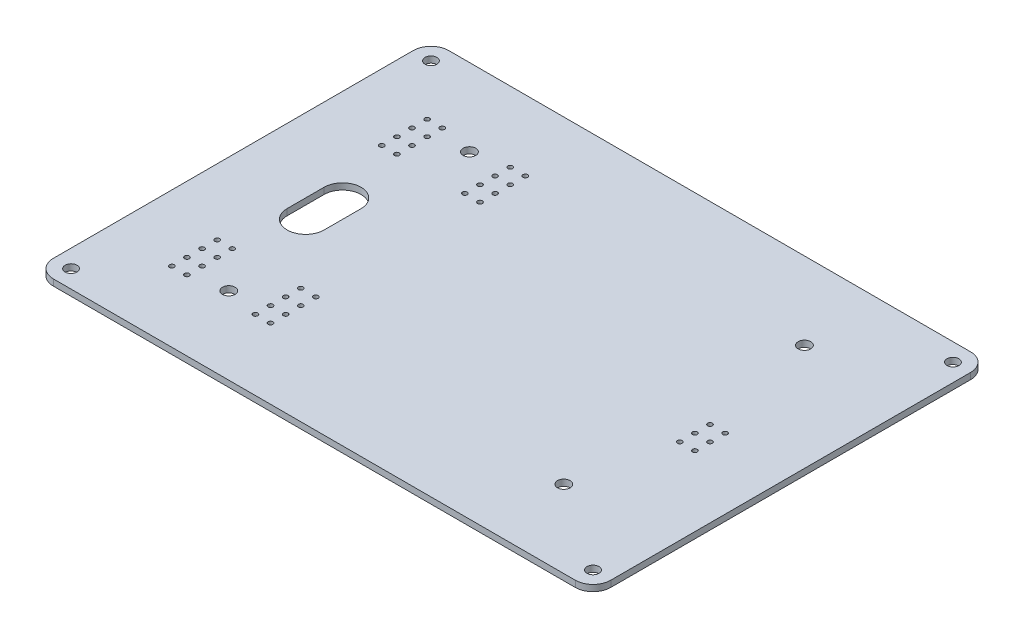
SolidWorks part; units mm, degrees
material "A-Glass Fiber"
ref_plane "Front Plane" through (0, 0, 0) normal (0, 0, 1) x (1, 0, 0)
ref_plane "Top Plane" through (0, 0, 0) normal (0, 1, 0) x (1, 0, 0)
ref_plane "Right Plane" through (0, 0, 0) normal (1, 0, 0) x (0, 0, -1)
sketch "Sketch1" plane through (0, 0, 0) normal (0, 1, 0) x (1, 0, 0)
  line L0 (0, 0) -> (70.7165, 0) construction
  line L1 (-65.4106, -49.8688) -> (66.2376, -49.8688)
  line L2 (-69.8896, -45.3898) -> (-69.8896, 45.3898)
  line L3 (-65.4106, 49.8688) -> (66.2376, 49.8688)
  line L4 (70.7165, -45.3898) -> (70.7165, 45.3898)
  line L5 (-69.8896, -49.8688) -> (70.7165, 49.8688) construction
  line L6 (-69.8896, 49.8688) -> (70.7165, -49.8688) construction
  line L10 (-71.1596, 54.5719) -> (-71.1596, 45.5295) construction
  arc A0 (-69.8896, 45.3898) -> (-65.4106, 49.8688) centre (-65.4106, 45.3898) cw
  arc A1 (66.2376, 49.8688) -> (70.7165, 45.3898) centre (66.2376, 45.3898) cw
  arc A2 (70.7165, -45.3898) -> (66.2376, -49.8688) centre (66.2376, -45.3898) cw
  arc A3 (-65.4106, -49.8688) -> (-69.8896, -45.3898) centre (-65.4106, -45.3898) cw
  point P0 (0.4135, 0)
  point P8 (66.2581, 45.3898)
  point P9 (-67.329, 45.3898)
  point P12 (0, 0)
  point P13 (-68.7024, 48.7021)
  point P15 (-70.1912, 50.1909)
  dimension "D1" = 1.27
extrude "Boss-Extrude1" add sketch "Sketch1" against normal blind 1.5875
sketch "Sketch2" plane through (0, 0, 0) normal (0, 1, 0) x (1, 0, 0)
  circle A35 centre (-40.6725, -30.35) radius 1.5875
  circle A36 centre (-40.6725, -30.35) radius 1.5875
  circle A37 centre (-40.6725, 30.35) radius 1.5875
  circle A38 centre (-40.6725, 30.35) radius 1.5875
  circle A39 centre (43.8275, 30.35) radius 1.5875
  circle A40 centre (43.8275, 30.35) radius 1.5875
  circle A41 centre (43.8275, -30.35) radius 1.5875
  circle A42 centre (43.8275, -30.35) radius 1.5875
  dimension "D27" = 0
  dimension "D28" = 0
  dimension "D29" = 0
  dimension "D30" = 0
extrude "Cut-Extrude1" cut sketch "Sketch2" against normal through all
sketch "Sketch3" plane through (0, 0, 0) normal (0, 1, 0) x (1, 0, 0)
  line L5 (-46.6035, 4.285) -> (-46.6035, -5.035) construction
  line L6 (-41.9335, 4.285) -> (-41.9335, -5.035)
  line L7 (-51.2735, 4.285) -> (-51.2735, -5.035)
  line L17 (-43.2035, 3.375) -> (-41.9335, 3.375) construction
  line L18 (-44.8535, 7.2) -> (-44.1998, 8.2889) construction
  line L19 (-46.6035, 7.2) -> (-46.6035, 8.955) construction
  line L20 (-44.8535, 7.2) -> (-48.3535, 7.2) construction
  line L21 (-46.6035, -7.95) -> (-46.6035, -9.705) construction
  line L22 (-48.3535, -7.95) -> (-44.8535, -7.95) construction
  arc A13 (-41.9335, 4.285) -> (-51.2735, 4.285) centre (-46.6035, 4.285) ccw
  arc A14 (-51.2735, -5.035) -> (-41.9335, -5.035) centre (-46.6035, -5.035) ccw
  arc A17 (-44.8535, 0.46) -> (-44.8535, 6.29) centre (-46.6035, 3.375) ccw construction
  point P2 (-46.6035, -0.375)
  dimension "D1" = 1.27
extrude "Cut-Extrude2" cut sketch "Sketch3" against normal through all
sketch "Sketch4" plane through (0, -1.5875, 0) normal (0, -1, 0) x (1, 0, 0)
  line L4 (-34.35, -10.348) -> (-39.27, -10.348)
  line L5 (-34.35, -25.08) -> (-34.35, -10.348)
  line L6 (-39.27, -25.08) -> (-34.35, -25.08)
  line L7 (-39.27, -10.348) -> (-39.27, -25.08)
  line L8 (-34.35, -10.348) -> (-39.27, -10.348)
  line L9 (-34.35, -25.08) -> (-34.35, -10.348)
  line L10 (-39.27, -25.08) -> (-34.35, -25.08)
  line L11 (-39.27, -10.348) -> (-39.27, -25.08)
  line L12 (-34.35, 25.63) -> (-39.27, 25.63)
  line L13 (-34.35, 10.898) -> (-34.35, 25.63)
  line L14 (-39.27, 10.898) -> (-34.35, 10.898)
  line L15 (-39.27, 25.63) -> (-39.27, 10.898)
  line L16 (-34.35, 25.63) -> (-39.27, 25.63)
  line L17 (-34.35, 10.898) -> (-34.35, 25.63)
  line L18 (-39.27, 10.898) -> (-34.35, 10.898)
  line L19 (-39.27, 25.63) -> (-39.27, 10.898)
  line L20 (-44.42, 10.898) -> (-39.5, 10.898)
  line L21 (-39.5, 10.898) -> (-39.5, 25.63)
  line L22 (-39.5, 25.63) -> (-44.42, 25.63)
  line L23 (-44.42, 25.63) -> (-44.42, 10.898)
  line L24 (-44.42, 10.898) -> (-39.5, 10.898)
  line L25 (-39.5, 10.898) -> (-39.5, 25.63)
  line L26 (-39.5, 25.63) -> (-44.42, 25.63)
  line L27 (-44.42, 25.63) -> (-44.42, 10.898)
  line L28 (-39.5, -10.348) -> (-44.42, -10.348)
  line L29 (-39.5, -25.08) -> (-39.5, -10.348)
  line L30 (-44.42, -25.08) -> (-39.5, -25.08)
  line L31 (-44.42, -10.348) -> (-44.42, -25.08)
  line L32 (-39.5, -10.348) -> (-44.42, -10.348)
  line L33 (-39.5, -25.08) -> (-39.5, -10.348)
  line L34 (-44.42, -25.08) -> (-39.5, -25.08)
  line L35 (-44.42, -10.348) -> (-44.42, -25.08)
  line L36 (35.46, 13.148) -> (40.38, 13.148)
  line L37 (35.46, 27.88) -> (35.46, 13.148)
  line L38 (40.38, 27.88) -> (35.46, 27.88)
  line L39 (40.38, 13.148) -> (40.38, 27.88)
  line L40 (35.46, 13.148) -> (40.38, 13.148)
  line L41 (35.46, 27.88) -> (35.46, 13.148)
  line L42 (40.38, 27.88) -> (35.46, 27.88)
  line L43 (40.38, 13.148) -> (40.38, 27.88)
  dimension "D1" = 0
  dimension "D2" = 0
  dimension "D3" = 0
  dimension "D4" = 0
  dimension "D5" = 0
sketch "Sketch6" plane through (0, -1.5875, 0) normal (0, -1, 0) x (1, 0, 0)
  line L0 (-20.19, 27.65) -> (-20.19, 33.65) construction
  line L1 (-20.19, 33.65) -> (-14.19, 33.65) construction
  line L2 (-14.19, 33.65) -> (-14.19, 27.65) construction
  line L3 (-14.19, 27.65) -> (-20.19, 27.65) construction
  line L4 (33.69, -6.45) -> (33.69, -22.45)
  line L5 (54.59, -6.45) -> (33.69, -6.45)
  line L6 (54.59, -22.45) -> (54.59, -6.45)
  line L7 (33.69, -22.45) -> (54.59, -22.45)
  line L8 (33.69, -6.45) -> (33.69, -22.45)
  line L9 (54.59, -6.45) -> (33.69, -6.45)
  line L10 (54.59, -22.45) -> (54.59, -6.45)
  line L11 (33.69, -22.45) -> (54.59, -22.45)
  line L20 (-8.69, 27.65) -> (-8.69, 33.65) construction
  line L21 (-8.69, 33.65) -> (-2.69, 33.65) construction
  line L22 (-2.69, 33.65) -> (-2.69, 27.65) construction
  line L23 (-2.69, 27.65) -> (-8.69, 27.65) construction
  line L24 (-20.19, 27.65) -> (-20.19, 33.65)
  line L25 (-20.19, 33.65) -> (-14.19, 33.65)
  line L26 (-14.19, 33.65) -> (-14.19, 27.65)
  line L27 (-14.19, 27.65) -> (-20.19, 27.65)
  line L28 (-8.69, 27.65) -> (-8.69, 33.65)
  line L29 (-8.69, 33.65) -> (-2.69, 33.65)
  line L30 (-2.69, 33.65) -> (-2.69, 27.65)
  line L31 (-2.69, 27.65) -> (-8.69, 27.65)
  line L80 (55.31, -35.15) -> (55.31, 35.15)
  line L82 (55.31, 35.15) -> (-55.31, 35.15)
  line L84 (-55.31, 35.15) -> (-55.31, -35.15)
  line L86 (-55.31, -35.15) -> (55.31, -35.15)
  line L92 (55.31, -35.15) -> (55.31, 35.15)
  line L94 (55.31, 35.15) -> (-55.31, 35.15)
  line L96 (-55.31, 35.15) -> (-55.31, -35.15)
  line L98 (-55.31, -35.15) -> (55.31, -35.15)
  circle A0 centre (-17.19, 30.65) radius 1.75 construction
  circle A1 centre (-5.69, 30.65) radius 1.75 construction
  circle A2 centre (-17.19, 30.65) radius 1.75
  circle A3 centre (-5.69, 30.65) radius 1.75
  dimension "D1" = 0
  dimension "D2" = 0
sketch "Sketch7" plane through (0, -1.5875, 0) normal (0, -1, 0) x (1, 0, 0)
  circle A1 centre (49.2175, 6.483) radius 0.6
  circle A2 centre (49.2175, 6.483) radius 0.6
  circle A3 centre (-49.3085, -32.125) radius 0.6
  circle A4 centre (-49.3085, -32.125) radius 0.6
  circle A5 centre (-28.3535, -32.125) radius 0.6
  circle A6 centre (-28.3535, -32.125) radius 0.6
  circle A7 centre (-28.3535, 20.707) radius 0.6
  circle A8 centre (-28.3535, 20.707) radius 0.6
  circle A9 centre (-49.4355, 20.707) radius 0.6
  circle A10 centre (-49.4355, 20.707) radius 0.6
  circle A11 centre (-32.1635, 20.707) radius 0.6
  circle A12 centre (-32.1635, 20.707) radius 0.6
  circle A13 centre (-53.2455, 20.707) radius 0.6
  circle A14 centre (-53.2455, 20.707) radius 0.6
  circle A15 centre (-32.1635, 28.327) radius 0.6
  circle A16 centre (-32.1635, 28.327) radius 0.6
  circle A17 centre (-53.2455, 28.327) radius 0.6
  circle A18 centre (-53.2455, 28.327) radius 0.6
  circle A19 centre (-32.1635, 24.517) radius 0.6
  circle A20 centre (-32.1635, 24.517) radius 0.6
  circle A21 centre (-53.2455, 24.517) radius 0.6
  circle A22 centre (-53.2455, 24.517) radius 0.6
  circle A23 centre (-32.1635, -28.315) radius 0.6
  circle A24 centre (-32.1635, -28.315) radius 0.6
  circle A25 centre (-53.1185, -28.315) radius 0.6
  circle A26 centre (-53.1185, -28.315) radius 0.6
  circle A27 centre (-32.1635, -32.125) radius 0.6
  circle A28 centre (-32.1635, -32.125) radius 0.6
  circle A29 centre (-53.1185, -32.125) radius 0.6
  circle A30 centre (-53.1185, -32.125) radius 0.6
  circle A31 centre (-28.3535, 24.517) radius 0.6
  circle A32 centre (-28.3535, 24.517) radius 0.6
  circle A33 centre (-49.4355, 24.517) radius 0.6
  circle A34 centre (-49.4355, 24.517) radius 0.6
  circle A35 centre (-32.1635, 32.137) radius 0.6
  circle A36 centre (-32.1635, 32.137) radius 0.6
  circle A37 centre (-53.2455, 32.137) radius 0.6
  circle A38 centre (-53.2455, 32.137) radius 0.6
  circle A39 centre (-32.1635, -20.695) radius 0.6
  circle A40 centre (-32.1635, -20.695) radius 0.6
  circle A41 centre (-53.1185, -20.695) radius 0.6
  circle A42 centre (-53.1185, -20.695) radius 0.6
  circle A43 centre (-32.1635, -24.505) radius 0.6
  circle A44 centre (-32.1635, -24.505) radius 0.6
  circle A45 centre (-53.1185, -24.505) radius 0.6
  circle A46 centre (-53.1185, -24.505) radius 0.6
  circle A47 centre (-28.3535, 32.137) radius 0.6
  circle A48 centre (-28.3535, 32.137) radius 0.6
  circle A49 centre (-49.4355, 32.137) radius 0.6
  circle A50 centre (-49.4355, 32.137) radius 0.6
  circle A51 centre (-28.3535, 28.327) radius 0.6
  circle A52 centre (-28.3535, 28.327) radius 0.6
  circle A53 centre (-49.4355, 28.327) radius 0.6
  circle A54 centre (-49.4355, 28.327) radius 0.6
  circle A55 centre (-28.3535, -24.505) radius 0.6
  circle A56 centre (-28.3535, -24.505) radius 0.6
  circle A57 centre (-49.3085, -24.505) radius 0.6
  circle A58 centre (-49.3085, -24.505) radius 0.6
  circle A59 centre (-28.3535, -28.315) radius 0.6
  circle A60 centre (-28.3535, -28.315) radius 0.6
  circle A61 centre (-49.3085, -28.315) radius 0.6
  circle A62 centre (-49.3085, -28.315) radius 0.6
  circle A63 centre (49.2175, 2.673) radius 0.6
  circle A64 centre (49.2175, 2.673) radius 0.6
  circle A65 centre (53.0275, -1.137) radius 0.6
  circle A66 centre (53.0275, -1.137) radius 0.6
  circle A67 centre (53.0275, 2.673) radius 0.6
  circle A68 centre (53.0275, 2.673) radius 0.6
  circle A69 centre (53.0275, 6.483) radius 0.6
  circle A70 centre (53.0275, 6.483) radius 0.6
  circle A71 centre (-28.3535, -20.695) radius 0.6
  circle A72 centre (-28.3535, -20.695) radius 0.6
  circle A73 centre (-49.3085, -20.695) radius 0.6
  circle A74 centre (-49.3085, -20.695) radius 0.6
  circle A75 centre (49.2175, -1.137) radius 0.6
  circle A76 centre (49.2175, -1.137) radius 0.6
  dimension "D1" = 0
  dimension "D2" = 0
  dimension "D3" = 0
  dimension "D4" = 0
  dimension "D5" = 0
  dimension "D6" = 0
  dimension "D7" = 0
  dimension "D8" = 0
  dimension "D9" = 0
  dimension "D10" = 0
  dimension "D11" = 0
  dimension "D12" = 0
  dimension "D13" = 0
  dimension "D14" = 0
  dimension "D15" = 0
  dimension "D16" = 0
  dimension "D17" = 0
  dimension "D18" = 0
  dimension "D19" = 0
  dimension "D20" = 0
  dimension "D21" = 0
  dimension "D22" = 0
  dimension "D23" = 0
  dimension "D24" = 0
  dimension "D25" = 0
  dimension "D26" = 0
  dimension "D27" = 0
  dimension "D28" = 0
  dimension "D29" = 0
  dimension "D30" = 0
  dimension "D31" = 0
  dimension "D32" = 0
  dimension "D33" = 0
  dimension "D34" = 0
  dimension "D35" = 0
  dimension "D36" = 0
  dimension "D37" = 0
  dimension "D38" = 0
extrude "Cut-Extrude3" cut sketch "Sketch7" against normal through all
sketch "Sketch8" plane through (0, -1.5875, 0) normal (0, -1, 0) x (1, 0, 0)
  line L4 (-48.1085, -18.395) -> (-54.9585, -18.395)
  line L5 (-48.1085, -34.425) -> (-48.1085, -18.395)
  line L6 (-54.9585, -34.425) -> (-48.1085, -34.425)
  line L7 (-54.9585, -18.395) -> (-54.9585, -34.425)
  line L8 (-48.1085, -18.395) -> (-54.9585, -18.395)
  line L9 (-48.1085, -34.425) -> (-48.1085, -18.395)
  line L10 (-54.9585, -34.425) -> (-48.1085, -34.425)
  line L11 (-54.9585, -18.395) -> (-54.9585, -34.425)
  line L12 (-55.0855, 18.407) -> (-48.2355, 18.407)
  line L13 (-48.2355, 18.407) -> (-48.2355, 34.437)
  line L14 (-48.2355, 34.437) -> (-55.0855, 34.437)
  line L15 (-55.0855, 34.437) -> (-55.0855, 18.407)
  line L16 (-55.0855, 18.407) -> (-48.2355, 18.407)
  line L17 (-48.2355, 18.407) -> (-48.2355, 34.437)
  line L18 (-48.2355, 34.437) -> (-55.0855, 34.437)
  line L19 (-55.0855, 34.437) -> (-55.0855, 18.407)
  line L20 (-34.0035, -18.395) -> (-34.0035, -34.425)
  line L21 (-34.0035, -34.425) -> (-27.1535, -34.425)
  line L22 (-27.1535, -34.425) -> (-27.1535, -18.395)
  line L23 (-27.1535, -18.395) -> (-34.0035, -18.395)
  line L24 (-34.0035, -18.395) -> (-34.0035, -34.425)
  line L25 (-34.0035, -34.425) -> (-27.1535, -34.425)
  line L26 (-27.1535, -34.425) -> (-27.1535, -18.395)
  line L27 (-27.1535, -18.395) -> (-34.0035, -18.395)
  line L28 (-27.1535, 34.437) -> (-34.0035, 34.437)
  line L29 (-27.1535, 18.407) -> (-27.1535, 34.437)
  line L30 (-34.0035, 18.407) -> (-27.1535, 18.407)
  line L31 (-34.0035, 34.437) -> (-34.0035, 18.407)
  line L32 (-27.1535, 34.437) -> (-34.0035, 34.437)
  line L33 (-27.1535, 18.407) -> (-27.1535, 34.437)
  line L34 (-34.0035, 18.407) -> (-27.1535, 18.407)
  line L35 (-34.0035, 34.437) -> (-34.0035, 18.407)
  line L36 (48.0175, 8.783) -> (48.0175, -3.437)
  line L37 (48.0175, -3.437) -> (54.8675, -3.437)
  line L38 (54.8675, -3.437) -> (54.8675, 8.783)
  line L39 (54.8675, 8.783) -> (48.0175, 8.783)
  line L40 (48.0175, 8.783) -> (48.0175, -3.437)
  line L41 (48.0175, -3.437) -> (54.8675, -3.437)
  line L42 (54.8675, -3.437) -> (54.8675, 8.783)
  line L43 (54.8675, 8.783) -> (48.0175, 8.783)
  dimension "D1" = 0
  dimension "D2" = 0
  dimension "D3" = 0
  dimension "D4" = 0
  dimension "D5" = 0
sketch "Sketch9" plane through (0, 0, 0) normal (0, 1, 0) x (1, 0, 0)
  circle A0 centre (-65.4106, 45.3898) radius 1.5
  circle A1 centre (-65.4106, -45.3898) radius 1.5
  circle A2 centre (66.2376, 45.3898) radius 1.5
  circle A3 centre (66.2376, -45.3898) radius 1.5
  dimension "D1" = 3
extrude "Cut-Extrude4" cut sketch "Sketch9" against normal through all
sketch "Sketch11" plane through (0, -1.5875, 0) normal (0, -1, 0) x (1, 0, 0)
  line L0 (-20.3246, -50.8932) -> (-20.3246, -38.1932) construction
  line L1 (-20.3246, -50.8932) -> (-20.3246, -38.1932)
sketch "Sketch12" plane through (0, -1.5875, 0) normal (0, -1, 0) x (1, 0, 0)
  circle A0 centre (-40.6725, -30.35) radius 3.81
  circle A1 centre (-40.6725, -30.35) radius 1.5875 construction
  circle A2 centre (-40.6725, 30.35) radius 3.81
  circle A3 centre (43.8275, 30.35) radius 3.81
  circle A4 centre (43.8275, -30.35) radius 3.81
  dimension "D1" = 7.62
equation "\"62.5mi\"=0.1"
